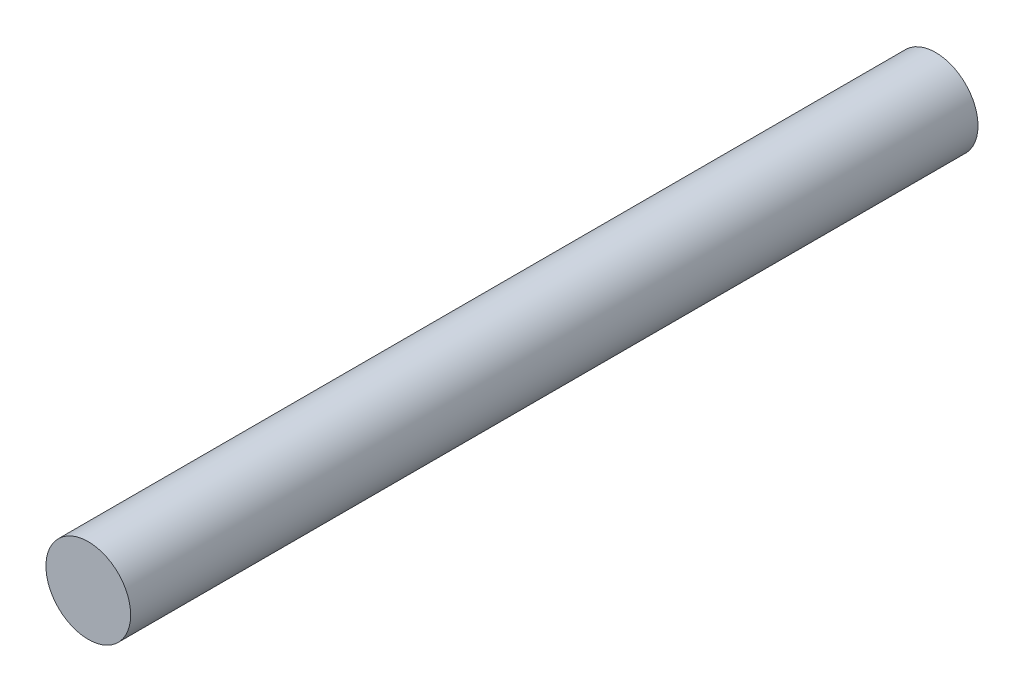
SolidWorks part; units mm, degrees
ref_plane "前视基准面" through (0, 0, 0) normal (0, 0, 1) x (1, 0, 0)
ref_plane "上视基准面" through (0, 0, 0) normal (0, 1, 0) x (1, 0, 0)
ref_plane "右视基准面" through (0, 0, 0) normal (1, 0, 0) x (0, 0, -1)
sketch "草图1" plane through (0, 0, 0) normal (0, 0, 1) x (1, 0, 0)
  circle A0 centre (0, 0) radius 10
  dimension "D1" = 20
extrude "凸台-拉伸1" add sketch "草图1" along normal blind 200
